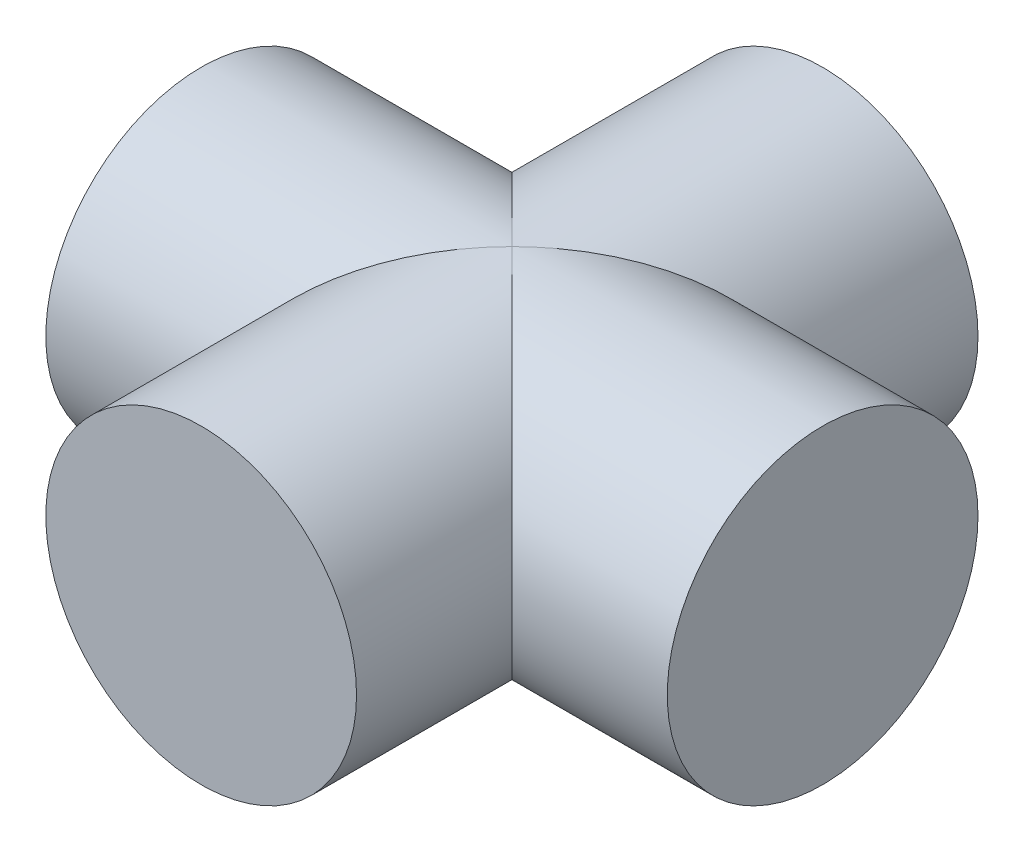
SolidWorks part; units mm, degrees
ref_plane "前视基准面" through (0, 0, 0) normal (0, 0, 1) x (1, 0, 0)
ref_plane "上视基准面" through (0, 0, 0) normal (0, 1, 0) x (1, 0, 0)
ref_plane "右视基准面" through (0, 0, 0) normal (1, 0, 0) x (0, 0, -1)
sketch "草图1" plane through (0, 0, 0) normal (0, 0, 1) x (1, 0, 0)
  circle A0 centre (0, 0) radius 5
extrude "凸台-拉伸1" add sketch "草图1" along normal blind 10 and the other way blind 10
sketch "草图2" plane through (0, 0, 0) normal (1, 0, 0) x (0, 0, -1)
  circle A0 centre (0, 0) radius 5
extrude "凸台-拉伸2" add sketch "草图2" along normal blind 10 and the other way blind 10
